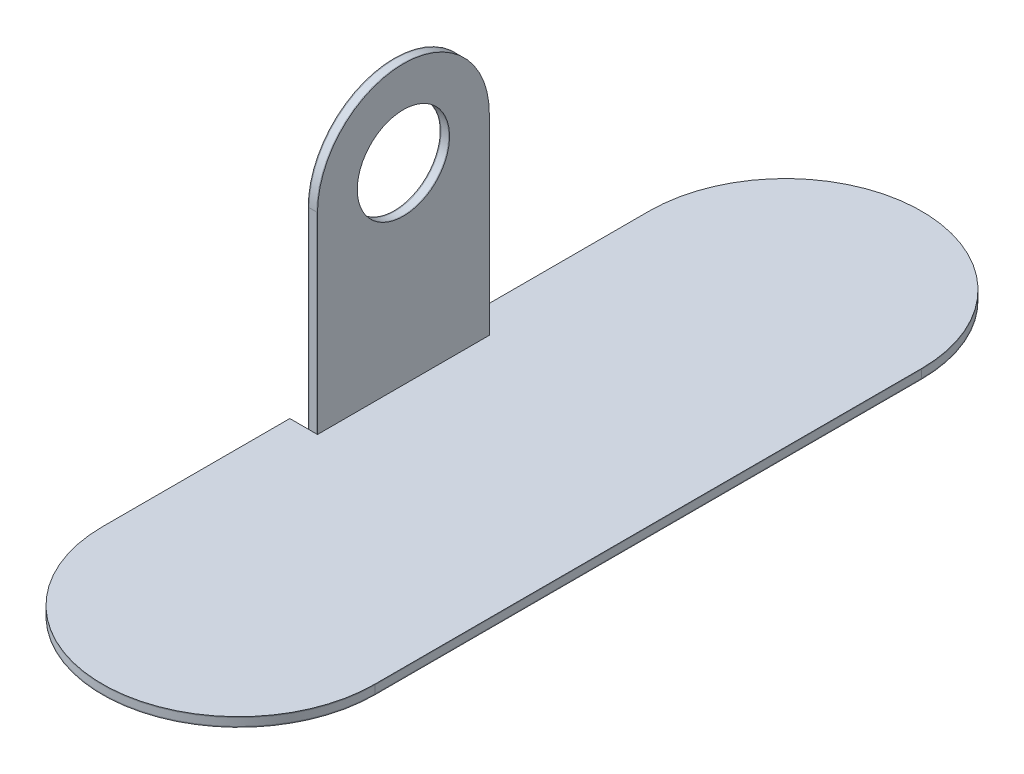
SolidWorks part; units mm, degrees
ref_plane "Front Plane" through (0, 0, 0) normal (0, 0, 1) x (1, 0, 0)
ref_plane "Top Plane" through (0, 0, 0) normal (0, 1, 0) x (1, 0, 0)
ref_plane "Right Plane" through (0, 0, 0) normal (1, 0, 0) x (0, 0, -1)
sketch "Sketch1" plane through (0, 0, 0) normal (0, 1, 0) x (1, 0, 0)
  line L0 (0, -88.9) -> (0, 88.9) construction
  line L1 (-44.323, 88.9) -> (-44.323, 27.94)
  line L2 (44.323, 88.9) -> (44.323, -88.9)
  line L3 (0, 0) -> (-35.323, 0) construction
  line L7 (-44.323, -27.94) -> (-44.323, -88.9)
  line L8 (-35.323, -27.94) -> (-35.323, 27.94)
  line L9 (-35.323, 27.94) -> (-44.323, 27.94)
  line L10 (-35.323, -27.94) -> (-44.323, -27.94)
  arc A0 (44.323, 88.9) -> (-44.323, 88.9) centre (0, 88.9) ccw
  arc A1 (-44.323, -88.9) -> (44.323, -88.9) centre (0, -88.9) ccw
  point P8 (0, 0)
  point P13 (-89.4761, 0)
  point P18 (-35.323, 0)
  dimension "D2" = 88.646
  dimension "D1" = 177.8
  dimension "D3" = 55.88
extrude "Boss-Extrude1" add sketch "Sketch1" along normal blind 0.25
sketch "Sketch2" plane through (0, 0.25, 0) normal (0, 1, 0) x (1, 0, 0)
  line L6 (-44.323, -27.94) -> (-44.323, -88.9)
  line L7 (44.323, -88.9) -> (44.323, 88.9)
  line L8 (-44.323, 88.9) -> (-44.323, 27.94)
  line L9 (-44.323, 27.94) -> (-35.323, 27.94)
  line L10 (-44.323, 27.94) -> (-35.323, 27.94)
  line L11 (-35.323, 27.94) -> (-35.323, -27.94)
  line L12 (-44.323, -27.94) -> (-44.323, -88.9)
  line L13 (44.323, -88.9) -> (44.323, 88.9)
  line L14 (-44.323, 88.9) -> (-44.323, 27.94)
  line L18 (-35.323, 27.94) -> (-35.323, -27.94)
  line L19 (-35.323, -27.94) -> (-44.323, -27.94)
  line L20 (-35.323, -27.94) -> (-44.323, -27.94)
  arc A2 (-44.323, -88.9) -> (44.323, -88.9) centre (0, -88.9) ccw
  arc A3 (44.323, 88.9) -> (-44.323, 88.9) centre (0, 88.9) ccw
  arc A4 (-44.323, -88.9) -> (44.323, -88.9) centre (0, -88.9) ccw
  arc A5 (44.323, 88.9) -> (-44.323, 88.9) centre (0, 88.9) ccw
  dimension "D1" = 0
extrude "Boss-Extrude2" add sketch "Sketch2" along normal blind 2.5 separate body
sketch "Sketch3" plane through (0, 2.75, 0) normal (0, 1, 0) x (1, 0, 0)
  line L6 (-35.323, -27.94) -> (-44.323, -27.94)
  line L7 (-44.323, -27.94) -> (-44.323, -88.9)
  line L8 (44.323, -88.9) -> (44.323, 88.9)
  line L9 (-44.323, 88.9) -> (-44.323, 27.94)
  line L10 (-35.323, -27.94) -> (-44.323, -27.94)
  line L11 (-44.323, 27.94) -> (-35.323, 27.94)
  line L13 (-44.323, -27.94) -> (-44.323, -88.9)
  line L14 (44.323, -88.9) -> (44.323, 88.9)
  line L15 (-44.323, 88.9) -> (-44.323, 27.94)
  line L18 (-44.323, 27.94) -> (-35.323, 27.94)
  line L19 (-35.323, 27.94) -> (-35.323, -27.94)
  line L20 (-35.323, 27.94) -> (-35.323, -27.94)
  arc A2 (-44.323, -88.9) -> (44.323, -88.9) centre (0, -88.9) ccw
  arc A3 (44.323, 88.9) -> (-44.323, 88.9) centre (0, 88.9) ccw
  arc A4 (-44.323, -88.9) -> (44.323, -88.9) centre (0, -88.9) ccw
  arc A5 (44.323, 88.9) -> (-44.323, 88.9) centre (0, 88.9) ccw
  dimension "D1" = 0
extrude "Boss-Extrude3" add sketch "Sketch3" along normal blind 0.25 separate body
ref_plane "Plane1" through (0, 3, 0) normal (0, 1, 0) x (1, 0, 0)
sketch "Sketch6" plane through (-35.323, 0, 0) normal (-1, 0, 0) x (0, 0, 1)
  line L0 (-27.94, 65.532) -> (-27.94, 0.25)
  line L1 (-27.94, 0.25) -> (27.94, 0)
  line L2 (27.94, 0) -> (27.94, 65.532)
  arc A0 (27.94, 65.532) -> (-27.94, 65.532) centre (0, 65.532) ccw
  circle A1 centre (0, 65.532) radius 15
  line M5 (-27.94, 0.25) -> (27.94, 0.25)
  line M6 (27.94, 0.25) -> (27.94, 2.75)
  line M7 (27.94, 2.75) -> (-27.94, 2.75)
  line M8 (-27.94, 2.75) -> (-27.94, 0.25)
  dimension "D1" = 55.88
  dimension "D3" = 30
  dimension "D2" = 65.532
extrude "Boss-Extrude5" add sketch "Sketch6" along normal blind 0.25 separate body contours L2 A0 L0 A1 M7 | M8 M5 M6 M7 | L1 L2 M5 region at (-35.323, 41.7992, 0) region at (-35.323, 1.5, 0) region at (-35.323, 0.1667, 9.3133)
sketch "Sketch7" plane through (-35.573, 0, 0) normal (-1, 0, 0) x (0, 0, 1)
  line L3 (27.94, 0) -> (27.94, 65.532)
  line L4 (-27.94, 65.532) -> (-27.94, 0.25)
  line L5 (-27.94, 0.25) -> (27.94, 0)
  line L6 (27.94, 0) -> (27.94, 65.532)
  line L7 (-27.94, 65.532) -> (-27.94, 0.25)
  line L8 (-27.94, 0.25) -> (27.94, 0)
  circle A0 centre (0, 65.532) radius 15 construction
  arc A1 (27.94, 65.532) -> (-27.94, 65.532) centre (0, 65.532) ccw
  arc A2 (27.94, 65.532) -> (-27.94, 65.532) centre (0, 65.532) ccw
  circle A3 centre (0, 65.532) radius 15
  circle M6 centre (0, 65.532) radius 15
  line M7 (27.94, 0) -> (27.94, 65.532)
  arc M8 (27.94, 65.532) -> (-27.94, 65.532) centre (0, 65.532) ccw
  line M9 (-27.94, 65.532) -> (-27.94, 0.25)
  line M10 (-27.94, 0.25) -> (27.94, 0)
  dimension "D1" = 0
extrude "Boss-Extrude7" add sketch "Sketch7" along normal blind 2.5 separate body contours M10 M7 M8 M9 M6 region at (-35.573, 40.3809, 0.0156)
sketch "Sketch8" plane through (-38.073, 0, 0) normal (-1, 0, 0) x (0, 0, 1)
  circle A1 centre (0, 65.532) radius 15
  circle A2 centre (0, 65.532) radius 15
  line M2 (-27.94, 0.25) -> (27.94, 0)
  line M3 (27.94, 0) -> (27.94, 65.532)
  arc M4 (27.94, 65.532) -> (-27.94, 65.532) centre (0, 65.532) ccw
  line M5 (-27.94, 65.532) -> (-27.94, 0.25)
  circle M6 centre (0, 65.532) radius 15
  dimension "D1" = 0
extrude "Boss-Extrude8" add sketch "Sketch8" along normal blind 0.25 separate body contours M5 M2 M3 M4 M6 region at (-38.073, 40.3809, 0.0156)
